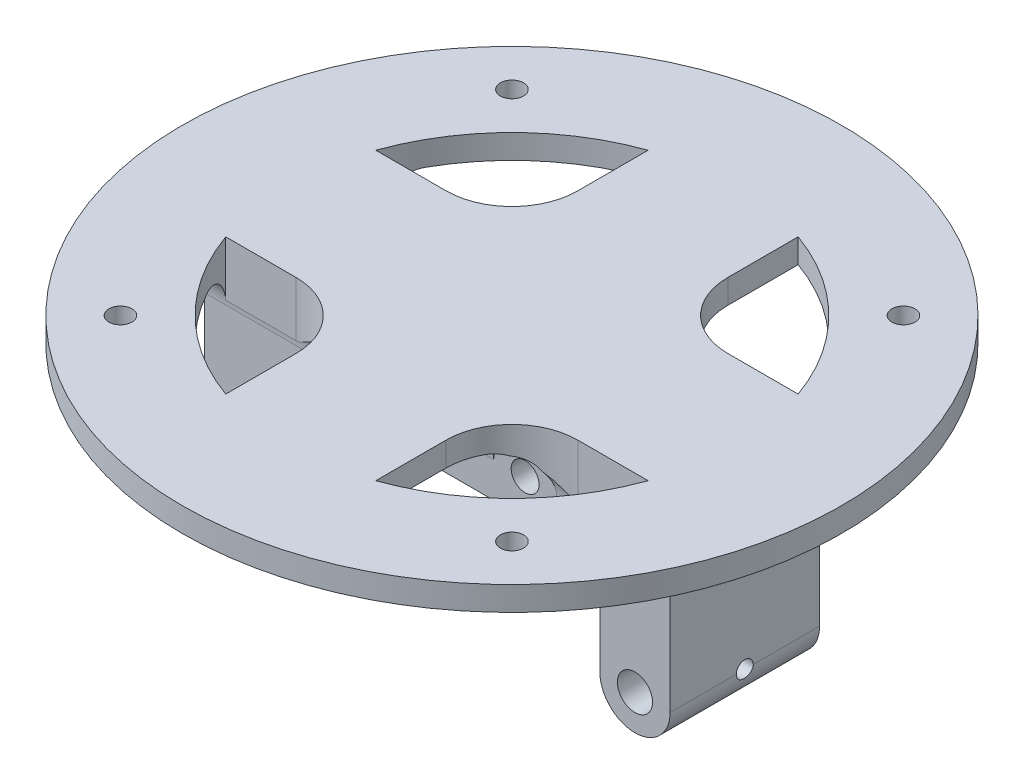
SolidWorks part; units mm, degrees
ref_plane "Front Plane" through (0, 0, 0) normal (0, 0, 1) x (1, 0, 0)
ref_plane "Top Plane" through (0, 0, 0) normal (0, 1, 0) x (1, 0, 0)
ref_plane "Right Plane" through (0, 0, 0) normal (1, 0, 0) x (0, 0, -1)
sketch "Sketch1" plane through (0, 0, 0) normal (0, 0, 1) x (1, 0, 0)
  line L7 (53, 17.7577) -> (53, 0)
  line L8 (0, 0) -> (0, 21.7577) construction
  line L15 (33, 37.7577) -> (-33, 37.7577)
  line L16 (20, 21.7577) -> (-20, 21.7577)
  line L17 (20, 21.7577) -> (34.5, 21.7577)
  line L18 (37, 0) -> (37, 19.2577)
  line L19 (-37, 0) -> (-37, 19.2577)
  line L20 (-20, 21.7577) -> (-34.5, 21.7577)
  line L21 (-53, 17.7577) -> (-53, 0)
  line L22 (0, 37.7577) -> (0, 42.1497) construction
  line L23 (33, 37.7577) -> (53, 37.7577)
  line L24 (53, 37.7577) -> (53, 17.7577)
  line L25 (-53, 17.7577) -> (-53, 37.7577)
  line L26 (-53, 37.7577) -> (-33, 37.7577)
  circle A0 centre (45, 0) radius 4
  circle A2 centre (20, 30) radius 3.175
  arc A6 (37, 0) -> (53, 0) centre (45, 0) ccw
  arc A10 (37, 19.2577) -> (34.5, 21.7577) centre (34.5, 19.2577) ccw
  arc A11 (-37, 19.2577) -> (-34.5, 21.7577) centre (-34.5, 19.2577) cw
  arc A13 (-37, 0) -> (-53, 0) centre (-45, 0) cw
  circle A14 centre (-20, 30) radius 3.175
  circle A15 centre (-45, 0) radius 4
  point P14 (45, 8)
  point P19 (28, 30)
  point P24 (0, 22)
  point P33 (-28, 30)
  point P34 (-45, 8)
  point P45 (0, 38)
  dimension "D1" = 8
  dimension "D2" = 6.35
  dimension "D3" = 16
  dimension "D4" = 2.5
  dimension "D6" = 45
  dimension "D7" = 20
  dimension "D8" = 30
  dimension "D9" = 16
extrude "Boss-Extrude2" add sketch "Sketch1" along normal blind 34 contours L16 L20 A11 L19 A13 L21 L25 L26 L15 L23 L24 L7 A6 L18 A10 L17 | A0 | A2 | A14 | A15
ref_plane "Plane1" through (0, 0, 14.22) normal (0, 0, 1) x (1, 0, 0)
sketch "Sketch5" plane through (53, 0, 0) normal (1, 0, 0) x (0, 0, -1)
  line L0 (-34, 0) -> (0, 0) construction
  circle A0 centre (-17, 0) radius 1.925
  dimension "D1" = 3.85
extrude "Cut-Extrude4" cut sketch "Sketch5" against normal blind 5.5562
mirror "Mirror2" about plane through (0, 0, 0) normal (1, 0, 0) of "Cut-Extrude4"
sketch "Sketch6" plane through (0, 37.7577, 0) normal (0, 1, 0) x (1, 0, 0)
  line L0 (0, -34) -> (0, 0) construction
  line L1 (-53, -34) -> (53, -34) construction
  line L2 (0, -17) -> (0, -187.5802) construction
  line L3 (0, -17) -> (-44.5477, -61.5477) construction
  line L4 (-53, -34) -> (-37, -34) construction
  line L5 (32.0754, -34.069) -> (48.0588, -34.069)
  line L6 (17.069, -49.0754) -> (17.069, -65.0588)
  line L7 (0, -17) -> (0, -39.7776) construction
  line L8 (0, -17) -> (-26.3065, -17) construction
  line L9 (-17.069, -49.0754) -> (-17.069, -65.0588)
  line L10 (-32.0754, -34.069) -> (-48.0588, -34.069)
  line L11 (17.069, 15.0754) -> (17.069, 31.0588)
  line L12 (32.0754, 0.069) -> (48.0588, 0.069)
  line L13 (-32.0754, 0.069) -> (-48.0588, 0.069)
  line L14 (-17.069, 15.0754) -> (-17.069, 31.0588)
  circle A0 centre (0, -17) radius 75
  circle A1 centre (-44.5477, -61.5477) radius 2.625
  circle A2 centre (-44.5477, 27.5477) radius 2.625
  circle A3 centre (44.5477, 27.5477) radius 2.625
  circle A4 centre (44.5477, -61.5477) radius 2.625
  arc A5 (17.069, -65.0588) -> (48.0588, -34.069) centre (0, -17) ccw
  arc A6 (32.0754, -34.069) -> (17.069, -49.0754) centre (32.0754, -49.0754) ccw
  arc A7 (-32.0754, -34.069) -> (-17.069, -49.0754) centre (-32.0754, -49.0754) cw
  arc A8 (-17.069, -65.0588) -> (-48.0588, -34.069) centre (0, -17) cw
  arc A9 (32.0754, 0.069) -> (17.069, 15.0754) centre (32.0754, 15.0754) cw
  arc A10 (17.069, 31.0588) -> (48.0588, 0.069) centre (0, -17) cw
  arc A11 (-17.069, 31.0588) -> (-48.0588, 0.069) centre (0, -17) ccw
  arc A12 (-32.0754, 0.069) -> (-17.069, 15.0754) centre (-32.0754, 15.0754) ccw
  dimension "D1" = 150
  dimension "D4" = 5.25
  dimension "D9" = 102
  dimension "D2" = 45
  dimension "D3" = 63
  dimension "D6" = 63
  dimension "D7" = 27.5477
  dimension "D8" = 27.5477
  dimension "D10" = 34.138
  dimension "D5" = 4
extrude "Boss-Extrude3" add sketch "Sketch6" along normal blind 5.5
fillet "Fillet1" radius 8 4 edges at (53, 37.7577, 17) (-53, 37.7577, 17) (0, 37.7577, 34) (0, 37.7577, 0)
sketch "Sketch7" plane through (0, 0, 0) normal (0, 0, -1) x (-1, 0, 0)
  circle A0 centre (20, 30) radius 7.15
  circle A1 centre (-20, 30) radius 7.15
  dimension "D1" = 14.3
  dimension "D2" = 14.3
extrude "Cut-Extrude8" cut sketch "Sketch7" along normal through all
ref_plane "Plane2" through (0, 0, 17) normal (0, 0, -1) x (-1, 0, 0)
mirror "Mirror3" about plane through (0, 0, 17) normal (0, 0, -1) of "Cut-Extrude8"
